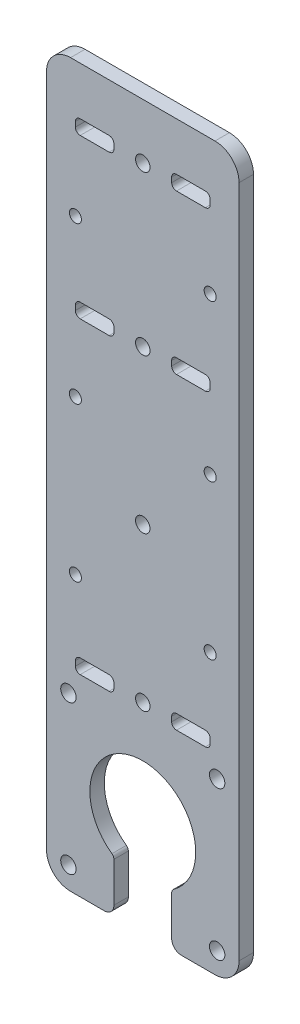
SolidWorks part; units mm, degrees
material "Acrylic (Medium-high impact)"
ref_plane "Front Plane" through (0, 0, 0) normal (0, 0, 1) x (1, 0, 0)
ref_plane "Top Plane" through (0, 0, 0) normal (0, 1, 0) x (1, 0, 0)
ref_plane "Right Plane" through (0, 0, 0) normal (1, 0, 0) x (0, 0, -1)
sketch "Sketch1" plane through (0, 0, 0) normal (0, 0, 1) x (1, 0, 0)
  line L0 (0, 75) -> (0, -75) construction
  line L1 (-20, 75) -> (20, 75)
  line L2 (-20, 75) -> (-20, -75)
  line L3 (-20, -75) -> (20, -75)
  line L4 (20, 75) -> (20, -75)
  line L5 (20, 0) -> (-20, 0) construction
  line L6 (0, -75) -> (0, -55) construction
  line L7 (0, -55) -> (6, -55) construction
  line L8 (6, -55) -> (6, -75) construction
  line L9 (0, -55) -> (-6, -55) construction
  line L10 (-6, -55) -> (-6, -75) construction
  line L11 (0, -55) -> (20, -75) construction
  line L12 (0, -55) -> (15.4503, -70.4503) construction
  line L13 (-6, -75) -> (-6, -64.2195)
  line L14 (6, -75) -> (6, -64.2195)
  line L15 (0, -75) -> (0, -35) construction
  line L16 (-20, -35) -> (20, -35) construction
  line L17 (0, -35) -> (0, -32) construction
  line L18 (-20, -32) -> (20, -32) construction
  circle A0 centre (0, -55) radius 11
  circle A1 centre (15.4503, -70.4503) radius 1.6
  circle A2 centre (-15.4503, -70.4503) radius 1.6
  circle A3 centre (-15.4503, -39.5497) radius 1.6
  circle A4 centre (15.4503, -39.5497) radius 1.6
  point P8 (0, 0)
  point P26 (0, -55)
  dimension "D1" = 4
extrude "Boss-Extrude1" add sketch "Sketch1" along normal blind 3 contours A0 L14 L3 L4 L1 L2 L13 A4 A3 A2 A1 region at (0, 5.617, 0)
fillet "Fillet1" radius 5 4 edges at (-20, -75, 1.5) (20, -75, 1.5) (-20, 75, 1.5) (20, 75, 1.5)
fillet "Fillet2" radius 2 2 edges at (6, -75, 1.5) (-6, -75, 1.5)
fillet "Fillet3" radius 1 2 edges at (6, -64.2195, 1.5) (-6, -64.2195, 1.5)
sketch "Sketch2" plane through (0, 0, 3) normal (0, 0, 1) x (1, 0, 0)
  line L0 (0, -75) -> (0, -35) construction
  line L1 (0, -35) -> (0, -33.5) construction
  line L2 (-20, -33.5) -> (20, -33.5) construction
  line L3 (-20, 70) -> (-20, -70) construction
  line L4 (20, 70) -> (20, -70) construction
  line L5 (-20, -35) -> (20, -35) construction
  line L6 (20, -35) -> (20, -32)
  line L7 (20, -32) -> (-20, -32) construction
  line L8 (-20, -32) -> (-20, -35)
  line L9 (0, 75) -> (0, 65) construction
  line L10 (-15, 75) -> (15, 75) construction
  line L11 (0, 65) -> (0, 62) construction
  line L12 (0, 62) -> (0, 32) construction
  line L13 (0, 32) -> (0, 29) construction
  line L14 (-20, 29) -> (20, 29) construction
  line L15 (20, 29) -> (20, 32) construction
  line L16 (20, 32) -> (-20, 32) construction
  line L17 (-20, 32) -> (-20, 29) construction
  line L18 (-20, 62) -> (20, 62) construction
  line L19 (20, 62) -> (20, 65) construction
  line L20 (-10, 65) -> (-10, -35) construction
  line L21 (-20, 65) -> (-20, 62) construction
  line L22 (-20, 65) -> (0, 65) construction
  line L23 (0, 65) -> (20, 65) construction
  line L24 (10, 65) -> (10, -35) construction
  line L25 (0, -33.5) -> (0, 30.5) construction
  line L26 (-10, 65) -> (-6, 65) construction
  line L27 (-10, 65) -> (-14, 65) construction
  line L28 (10, 65) -> (14, 65) construction
  line L29 (10, 65) -> (6, 65) construction
  line L30 (6, 65) -> (6, -35) construction
  line L31 (14, 65) -> (14, -35) construction
  line L32 (-14, 65) -> (-14, -35) construction
  line L33 (-6, 65) -> (-6, -35) construction
  line L34 (0, 29) -> (0, -32) construction
  line L35 (-14, 65) -> (-6, 65)
  line L36 (-14, 65) -> (-14, 62)
  line L37 (-14, 62) -> (-6, 62)
  line L38 (-6, 65) -> (-6, 62)
  line L39 (6, 65) -> (14, 65)
  line L40 (6, 65) -> (6, 62)
  line L41 (6, 62) -> (14, 62)
  line L42 (14, 65) -> (14, 62)
  line L43 (-14, 32) -> (-6, 32)
  line L44 (-14, 32) -> (-14, 29)
  line L45 (-14, 29) -> (-6, 29)
  line L46 (-6, 32) -> (-6, 29)
  line L47 (6, 32) -> (14, 32)
  line L48 (6, 32) -> (6, 29)
  line L49 (6, 29) -> (14, 29)
  line L50 (14, 32) -> (14, 29)
  line L51 (-14, -32) -> (-6, -32)
  line L52 (-14, -32) -> (-14, -35)
  line L53 (-14, -35) -> (-6, -35)
  line L54 (-6, -32) -> (-6, -35)
  line L55 (6, -32) -> (14, -32)
  line L56 (6, -32) -> (6, -35)
  line L57 (6, -35) -> (14, -35)
  line L58 (14, -32) -> (14, -35)
  circle A0 centre (0, -33.5) radius 1.5
  circle A1 centre (0, 30.5) radius 1.5
  circle A2 centre (0, 63.5) radius 1.5
  circle A3 centre (0, -1.5) radius 1.5
extrude "Cut-Extrude1" cut sketch "Sketch2" against normal blind 3 contours L54 L51 L52 L53 | L58 L55 L56 L57 | A0 | A1 | L50 L47 L48 L49 | L46 L43 L44 L45 | A2 | L38 L35 L36 L37 | L42 L39 L40 L41 | A3 region at (-10, 63.5, 3) region at (10, 63.5, 3) region at (-10, 30.5, 3) region at (10, 30.5, 3) region at (-10, -33.5, 3) region at (10, -33.5, 3) region at (0, -33.5, 3) region at (0, 30.5, 3) region at (0, 63.5, 3) region at (0, -1.5, 3)
fillet "Fillet4" radius 1 24 edges at (-6, 29, 1.5) (-14, 29, 1.5) (-6, 32, 1.5) (14, -35, 1.5) (6, -35, 1.5) (6, -32, 1.5) (14, -32, 1.5) (-6, -35, 1.5) (-14, -35, 1.5) (-14, -32, 1.5) (-6, -32, 1.5) (14, 29, 1.5) (6, 29, 1.5) (6, 32, 1.5) (14, 32, 1.5) (-14, 32, 1.5) (14, 65, 1.5) (14, 62, 1.5) (6, 65, 1.5) (6, 62, 1.5) (-14, 62, 1.5) (-6, 62, 1.5) (-6, 65, 1.5) (-14, 65, 1.5)
sketch "Sketch3" plane through (0, 0, 3) normal (0, 0, 1) x (1, 0, 0)
  line L0 (-14, 30.5) -> (-14, -1.5) construction
  line L1 (14, -1.5) -> (14, 30.5) construction
  line L2 (14, 31) -> (14, 30) construction
  line L3 (-14, 31) -> (-14, 30) construction
  line L4 (-14, -1.5) -> (-14, -33.5) construction
  line L5 (-14, -33) -> (-14, -34) construction
  line L6 (-14, -1.5) -> (14, -1.5) construction
  line L7 (14, -1.5) -> (14, -33.5) construction
  line L8 (14, -33) -> (14, -34) construction
  line L9 (-14, 30.5) -> (-14, 63.5) construction
  line L10 (-14, 64) -> (-14, 63) construction
  line L11 (14, 63.5) -> (14, 30.5) construction
  line L12 (14, 64) -> (14, 63) construction
  point P18 (-14, 47)
  point P21 (14, 47)
  point P22 (14, 14.5)
  point P23 (-14, 14.5)
  point P24 (-14, -17.5)
  point P25 (14, -17.5)
hole_wizard "Ø2.5 (2.5) Diameter Hole1" positions "Sketch7" profile "Sketch6" hole size "Ø2.5" standard "ISO"
sketch "Sketch7" plane through (0, 0, 3) normal (0, 0, 1) x (1, 0, 0)
  point P0 (14, -17.5)
  point P3 (-14, -17.5)
  point P6 (-14, 14.5)
  point P9 (14, 14.5)
  point P12 (14, 47)
  point P15 (-14, 47)
sketch "Sketch6" plane through (14, -17.5, 3) normal (1, 0, 0) x (0, -1, 0)
  line L0 (0, 0) -> (0, 6.7511)
  line L1 (0, 6.7511) -> (1.25, 6)
  line L2 (1.25, 6) -> (1.25, 0)
  line L5 (1.25, 0) -> (0, 0)
  line L10 (0, 6.7511) -> (-1.25, 6) construction
  line L11 (0, -6.35) -> (0, 107.95) construction
  dimension "Hole Dia." = 2.5
  dimension "Hole Depth" = 6
  dimension "Drill Angle" = 118
